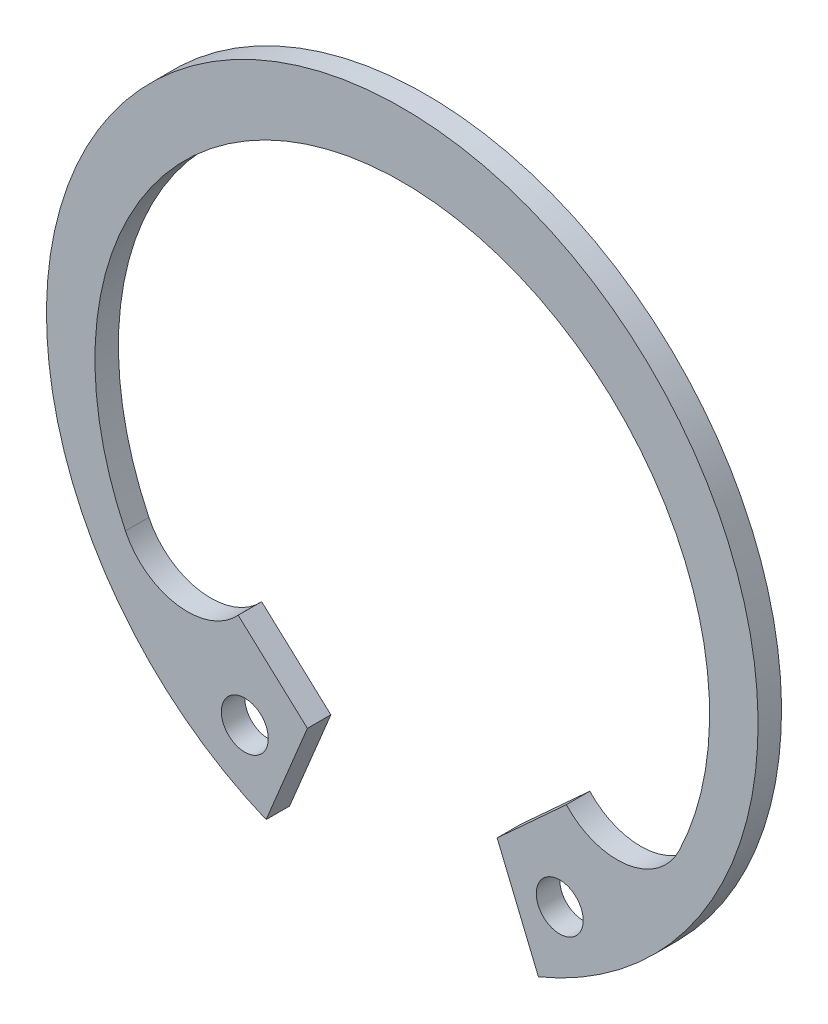
SolidWorks part; units mm, degrees
material "65Mn"
ref_plane "前视" through (0, 0, 0) normal (0, 0, 1) x (1, 0, 0)
ref_plane "上视" through (0, 0, 0) normal (0, 1, 0) x (1, 0, 0)
ref_plane "右视" through (0, 0, 0) normal (1, 0, 0) x (0, 0, -1)
sketch "草图1" plane through (0, 0, 0) normal (0, 0, 1) x (1, 0, 0)
  line L0 (0, -11.8766) -> (0, 11.8063) construction
  line L1 (0, 0) -> (-4.6199, -11.1535) construction
  line L2 (-10.4916, -10.5925) -> (-6.0655, -14.6435)
  line L3 (-6.0655, -14.6435) -> (-8.706, -21.0183)
  line L4 (6.0655, -14.6435) -> (8.706, -21.0183)
  line L5 (10.4916, -10.5925) -> (6.0655, -14.6435)
  arc A0 (8.706, -21.0183) -> (-8.706, -21.0183) centre (0, 0) ccw
  arc A1 (17.7009, -9.5324) -> (-17.7009, -9.5324) centre (0, -1) ccw
  circle A2 centre (-10.0677, -16.4661) radius 1.5
  arc A3 (-17.7009, -9.5324) -> (-10.4916, -10.5925) centre (-13.7373, -7.6218) ccw
  circle A4 centre (10.0677, -16.4661) radius 1.5
  arc A5 (17.7009, -9.5324) -> (10.4916, -10.5925) centre (13.7373, -7.6218) cw
  dimension "D1" = 45.5
  dimension "D2" = 39.3
  dimension "D4" = 3
  dimension "D5" = 4.4
  dimension "D3" = 1
  dimension "D6" = 6.9
  dimension "D7" = 6
  dimension "D9" = 19.3
  dimension "D10" = 3
  dimension "D8" = 22.5
sketch "尺寸草图" plane through (0, 0, 0) normal (0, 0, 1) x (1, 0, 0)
  line L0 (-22.75, 0) -> (22.75, 0) construction
  line L1 (0, 0) -> (29.4981, -33.9833) construction
  circle A2 centre (0, 0) radius 22.75
  point P9 (16.55, 0)
  point P10 (17.55, 0)
  point P11 (-14.9, 0)
  point P12 (-10.3, 0)
  point P13 (6.9, 0)
  point P14 (-16.3, 0)
  point P15 (-22.3, 0)
  point P16 (-19.3, 0)
  point P18 (0.9833, -1.1328)
  dimension "DD" = 45.5
  dimension "d" = 39.3
  dimension "c" = 1
  dimension "R" = 19.3
  dimension "d1" = 3
  dimension "a" = 6.9
  dimension "B" = 6
  dimension "R2" = 4.4
  dimension "s" = 1.5
  dimension "B1" = 3
  dimension "aa" = 45
extrude "基体-拉伸" add sketch "草图1" along normal blind 0.75 and the other way blind 0.75
equation "\"D1@草图1\" = \"DD@尺寸草图\""
equation "\"D2@草图1\" = \"d@尺寸草图\""
equation "\"D5@草图1\" = \"R2@尺寸草图\""
equation "\"D9@草图1\" = \"R@尺寸草图\""
equation "\"D7@草图1\" = \"B@尺寸草图\""
equation "\"D10@草图1\" = \"B1@尺寸草图\""
equation "\"D4@草图1\" = \"d1@尺寸草图\""
equation "\"D6@草图1\" = \"a@尺寸草图\""
equation "\"D8@草图1\" = \"aa@尺寸草图\"/2"
equation "\"D3@草图1\" = \"c@尺寸草图\""
equation "\"D1@基体-拉伸\"=\"s@尺寸草图\"/2"
equation "\"D2@基体-拉伸\" = \"D1@基体-拉伸\""
